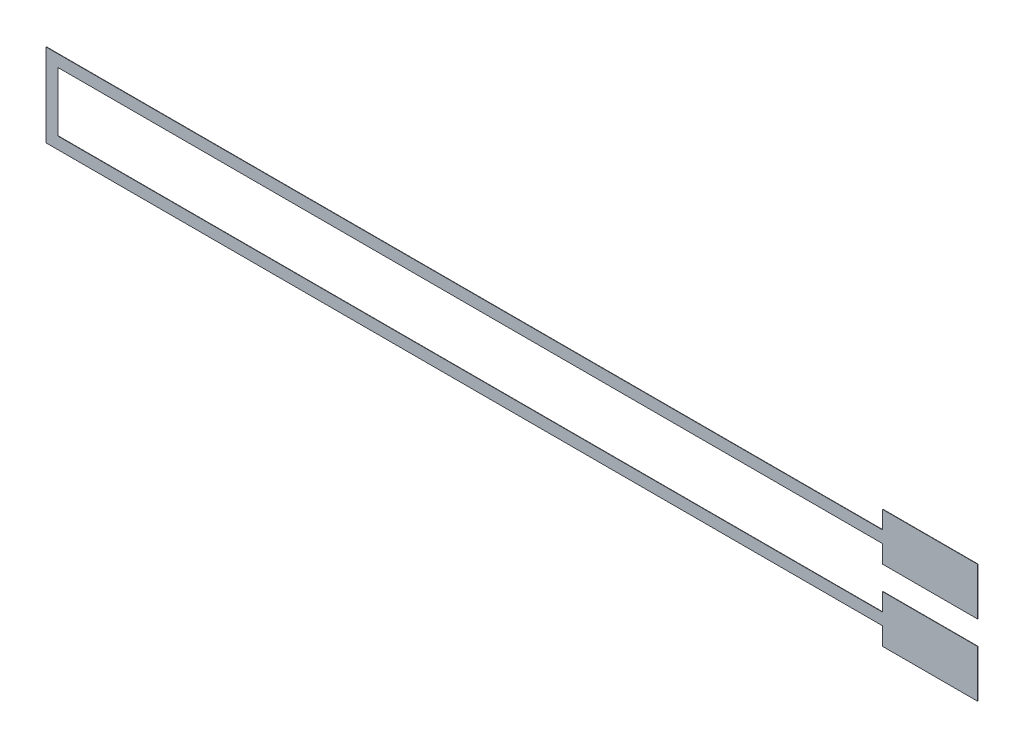
SolidWorks part; units mm, degrees
material "Pure Silver"
ref_plane "Front Plane" through (0, 0, 0) normal (0, 0, 1) x (1, 0, 0)
ref_plane "Top Plane" through (0, 0, 0) normal (0, 1, 0) x (1, 0, 0)
ref_plane "Right Plane" through (0, 0, 0) normal (1, 0, 0) x (0, 0, -1)
sketch "Sketch1" plane through (0, 0, 0) normal (0, 0, 1) x (1, 0, 0)
  line L0 (0, -1.5) -> (0, 1.5) construction
  line L2 (-2, 0.5) -> (2, 0.5)
  line L3 (-2, 0.5) -> (-2, 2.5)
  line L4 (-2, 2.5) -> (2, 2.5)
  line L5 (2, 0.5) -> (2, 2.5)
  line L6 (-2, 0.5) -> (2, 2.5) construction
  line L7 (-2, 2.5) -> (2, 0.5) construction
  line L8 (-2, -2.5) -> (2, -2.5)
  line L9 (-2, -2.5) -> (-2, -0.5)
  line L10 (-2, -0.5) -> (2, -0.5)
  line L11 (2, -2.5) -> (2, -0.5)
  line L12 (-2, -2.5) -> (2, -0.5) construction
  line L13 (-2, -0.5) -> (2, -2.5) construction
  point P4 (0, 0)
  dimension "D1" = 2
  dimension "D2" = 4
  dimension "D3" = 2
  dimension "D5" = 3
  dimension "D12" = 4
extrude "Boss-Extrude2" add sketch "Sketch1" along normal blind 0.015
sketch "Sketch4" plane through (0, 0, 0) normal (0, 0, 1) x (1, 0, 0)
  line L0 (-2, -1.5) -> (-2.75, -1.5) construction
  line L2 (-3, -1.75) -> (-3, -2) construction
  line L3 (-3, -2) -> (-4, -2) construction
  line L4 (-4, -2) -> (-4, -1) construction
  line L5 (-4, -1) -> (-5, -1) construction
  line L22 (-5, -1) -> (-5, -1.5) construction
  line L23 (-2, -0.5) -> (-2, -2.5) construction
  line L24 (-2, -0.5) -> (-2, -2.5)
  line L25 (-2, -1.2) -> (-2.75, -1.2)
  line L30 (-3.3, -1.75) -> (-3.3, -2)
  line L31 (-3.7, -2) -> (-3.7, -1)
  line L32 (-5.3, -1) -> (-5.3, -1.5)
  line L33 (-2, -1.8) -> (-2.7, -1.8)
  line L34 (-2.7, -1.8) -> (-2.7, -2)
  line L35 (-4.3, -2) -> (-4.3, -1)
  line L36 (-4.7, -1) -> (-4.7, -1.5)
  line L37 (-5.3, -1.5) -> (-4.7, -1.5)
  arc A0 (-2.75, -1.5) -> (-3, -1.75) centre (-2.75, -1.75) ccw construction
  arc A1 (-5, -1) -> (-4, -1) centre (-4.5, -1) cw construction
  arc A2 (-4, -2) -> (-3, -2) centre (-3.5, -2) ccw construction
  arc A15 (-2.75, -1.2) -> (-3.3, -1.75) centre (-2.75, -1.75) ccw
  arc A16 (-3.7, -2) -> (-3.3, -2) centre (-3.5, -2) ccw
  arc A17 (-5.3, -1) -> (-3.7, -1) centre (-4.5, -1) cw
  arc A18 (-2.7, -1.8) -> (-2.7, -1.8) centre (-2.7, -1.8) ccw
  arc A19 (-4.3, -2) -> (-2.7, -2) centre (-3.5, -2) ccw
  arc A20 (-4.7, -1) -> (-4.3, -1) centre (-4.5, -1) cw
  point P9 (-3, -1.5)
  dimension "D5" = 1
  dimension "D7" = 0.25
  dimension "D8" = 0.5
  dimension "D9" = 0.5
  dimension "D1" = 1
  dimension "D2" = 0.5
  dimension "D3" = 1
  dimension "D4" = 1
  dimension "D6" = 0.5
  dimension "D11" = 0.3
  dimension "D10" = 0.3
extrude "Boss-Extrude4" [suppressed] add sketch "Sketch4" along normal blind 0.015
sketch "Sketch7" plane through (0, 0, 0) normal (0, 0, 1) x (1, 0, 0)
  line L0 (-2, 1.5) -> (-2.75, 1.5) construction
  line L1 (-3, 1.75) -> (-3, 2) construction
  line L2 (-3, 2) -> (-4, 2) construction
  line L3 (-4, 2) -> (-4, 1) construction
  line L4 (-4, 1) -> (-5, 1) construction
  line L5 (-5, 1) -> (-5, 1.5) construction
  line L21 (-2, 1.8) -> (-2.7, 1.8)
  line L22 (-2.7, 1.8) -> (-2.7, 2)
  line L23 (-4.3, 2) -> (-4.3, 1)
  line L24 (-4.7, 1) -> (-4.7, 1.5)
  line L25 (-2, 1.2) -> (-2.75, 1.2)
  line L30 (-3.3, 1.75) -> (-3.3, 2)
  line L31 (-3.7, 2) -> (-3.7, 1)
  line L32 (-5.3, 1) -> (-5.3, 1.5)
  line L33 (-5.3, 1.5) -> (-4.7, 1.5)
  line L34 (-2, 2.5) -> (-2, 0.5) construction
  line L35 (-2, 2.5) -> (-2, 0.5)
  arc A0 (-5, 1) -> (-4, 1) centre (-4.5, 1) ccw construction
  arc A1 (-4, 2) -> (-3, 2) centre (-3.5, 2) cw construction
  arc A2 (-2.75, 1.5) -> (-3, 1.75) centre (-2.75, 1.75) cw construction
  arc A15 (-2.7, 1.8) -> (-2.7, 1.8) centre (-2.7, 1.8) cw
  arc A16 (-4.3, 2) -> (-2.7, 2) centre (-3.5, 2) cw
  arc A17 (-4.7, 1) -> (-4.3, 1) centre (-4.5, 1) ccw
  arc A18 (-2.75, 1.2) -> (-3.3, 1.75) centre (-2.75, 1.75) cw
  arc A19 (-3.7, 2) -> (-3.3, 2) centre (-3.5, 2) cw
  arc A20 (-5.3, 1) -> (-3.7, 1) centre (-4.5, 1) ccw
  point P13 (-3, 1.5)
  dimension "D5" = 1
  dimension "D7" = 0.5
  dimension "D8" = 0.5
  dimension "D3" = 1
  dimension "D9" = 0.25
  dimension "D1" = 1
  dimension "D2" = 0.5
  dimension "D4" = 1
  dimension "D6" = 0.5
  dimension "D11" = 0.3
  dimension "D10" = 0.3
extrude "Boss-Extrude9" [suppressed] add sketch "Sketch7" along normal blind 0.015
sketch "Sketch9" [suppressed] plane through (0, 0, 0) normal (0, 0, 1) x (1, 0, 0)
  line L2 (-5, -1.5) -> (-5, -2) construction
  line L3 (-5, -2) -> (-6, -2) construction
  line L4 (-6, -2) -> (-6, -1) construction
  line L5 (-6, -1) -> (-7, -1) construction
  line L6 (-7, -1) -> (-7, -1.5) construction
  line L7 (-5.3, -1.5) -> (-5.3, -2)
  line L8 (-5.7, -2) -> (-5.7, -1)
  line L9 (-7.3, -1) -> (-7.3, -1.5)
  line L10 (-4.7, -1.5) -> (-4.7, -2)
  line L11 (-6.3, -2) -> (-6.3, -1)
  line L12 (-6.7, -1) -> (-6.7, -1.5)
  line L13 (-7.3, -1.5) -> (-6.7, -1.5)
  line L14 (-5.3, -1.5) -> (-4.7, -1.5) construction
  line L15 (-5.3, -1.5) -> (-4.7, -1.5)
  arc A0 (-5, -2) -> (-6, -2) centre (-5.5, -2) cw construction
  arc A1 (-6, -1) -> (-7, -1) centre (-6.5, -1) ccw construction
  arc A2 (-5.3, -2) -> (-5.7, -2) centre (-5.5, -2) cw
  arc A3 (-5.7, -1) -> (-7.3, -1) centre (-6.5, -1) ccw
  arc A4 (-4.7, -2) -> (-6.3, -2) centre (-5.5, -2) cw
  arc A5 (-6.3, -1) -> (-6.7, -1) centre (-6.5, -1) ccw
  dimension "D6" = 0.5
  dimension "D7" = 0.5
  dimension "D1" = 0.5
  dimension "D2" = 1
  dimension "D3" = 1
  dimension "D4" = 1
  dimension "D5" = 0.5
  dimension "D8" = 0.3
  dimension "D9" = 0.3
extrude "Boss-Extrude10" [suppressed] add sketch "Sketch9" along normal up to surface (0.015 mm away) up to face at (0, -1.5, 0.015)
sketch "Sketch14" [suppressed] plane through (0, 0, 0.015) normal (0, 0, 1) x (1, 0, 0)
  line L1 (-5, 1.5) -> (-5, 2) construction
  line L2 (-5.3, 1.5) -> (-4.7, 1.5) construction
  line L3 (-5, 2) -> (-6, 2) construction
  line L4 (-6, 2) -> (-6, 1) construction
  line L5 (-6, 1) -> (-7, 1) construction
  line L6 (-7, 1) -> (-7, 1.5) construction
  line L7 (-4.7, 1.5) -> (-4.7, 2)
  line L8 (-6.3, 2) -> (-6.3, 1)
  line L9 (-6.7, 1) -> (-6.7, 1.5)
  line L10 (-5.3, 1.5) -> (-5.3, 2)
  line L11 (-5.7, 2) -> (-5.7, 1)
  line L12 (-7.3, 1) -> (-7.3, 1.5)
  line L13 (-7.3, 1.5) -> (-6.7, 1.5)
  arc A0 (-6, 2) -> (-5, 2) centre (-5.5, 2) cw construction
  arc A1 (-7, 1) -> (-6, 1) centre (-6.5, 1) ccw construction
  arc A2 (-6.3, 2) -> (-4.7, 2) centre (-5.5, 2) cw
  arc A3 (-6.7, 1) -> (-6.3, 1) centre (-6.5, 1) ccw
  arc A4 (-5.7, 2) -> (-5.3, 2) centre (-5.5, 2) cw
  arc A5 (-7.3, 1) -> (-5.7, 1) centre (-6.5, 1) ccw
  dimension "D6" = 0.5
  dimension "D7" = 0.5
  dimension "D1" = 0.5
  dimension "D2" = 1
  dimension "D3" = 1
  dimension "D4" = 1
  dimension "D5" = 0.5
  dimension "D8" = 0.3
  dimension "D9" = 0.3
extrude "Boss-Extrude16" [suppressed] add sketch "Sketch14" against normal up to surface (0.015 mm away) up to face at (0, 1.5, 0)
fillet "Fillet1" [suppressed] radius 0.25
fillet "Fillet2" [suppressed] radius 0.25
pattern_linear "LPattern3" [suppressed] count 16 spacing 2 of bodies 125 162
sketch "Sketch15" [suppressed] plane through (0, 0, 0.015) normal (0, 0, 1) x (1, 0, 0)
  line L0 (-36.3, 1) -> (-35.7, 1)
  line L1 (-35.7, -1) -> (-36.3, -1)
  line L2 (-36.3, -1) -> (-36.4846, -1)
  line L3 (-36.4846, -1) -> (-36.4846, -1.8714)
  line L4 (-36.4846, -1.8714) -> (-37.7365, -1.8714)
  line L5 (-37.7365, -1.8714) -> (-37.7365, 1.7158)
  line L6 (-37.7365, 1.7158) -> (-36.5999, 1.7158)
  line L7 (-36.5999, 1.7158) -> (-36.5999, 1)
  line L8 (-36.5999, 1) -> (-36.3, 1)
  line L9 (-35.7, -1) -> (-35.7, 1)
  arc A0 (-37.3, 1) -> (-35.7, 1) centre (-36.5, 1) ccw construction
  arc A1 (-35.7, -1) -> (-37.3, -1) centre (-36.5, -1) ccw construction
  arc A2 (-37.3, 1) -> (-35.7, 1) centre (-36.5, 1) ccw
  arc A3 (-35.7, -1) -> (-37.3, -1) centre (-36.5, -1) ccw
  arc A4 (-36.7, 1) -> (-36.3, 1) centre (-36.5, 1) ccw construction
  arc A5 (-36.3, -1) -> (-36.7, -1) centre (-36.5, -1) ccw construction
  arc A6 (-36.7, 1) -> (-36.3, 1) centre (-36.5, 1) ccw
  arc A7 (-36.3, -1) -> (-36.7, -1) centre (-36.5, -1) ccw
extrude "Cut-Extrude1" [suppressed] cut sketch "Sketch15" against normal through all contours L1 L9 L0 L8 L7 L6 L5 L4 L3 L2
sketch "Sketch16" [suppressed] plane through (0, 0, 0.015) normal (0, 0, 1) x (1, 0, 0)
  line L0 (-36.3, 1) -> (-35.7, 1) construction
  line L1 (-35.7, -1) -> (-36.3, -1) construction
  line L2 (-36.3, 1) -> (-35.7, 1)
  line L3 (-35.7, -1) -> (-36.3, -1)
  line L4 (-35.7, -1) -> (-35.7, 1)
  line L5 (-36.3, 1) -> (-36.3, -1)
extrude "Boss-Extrude17" [suppressed] add sketch "Sketch16" against normal up to surface (0.015 mm away) up to face at (0, 1.5, 0)
sketch "Sketch17" plane through (0, 0, 0) normal (0, 0, 1) x (1, 0, 0)
  line L0 (2, -2.5) -> (2, -0.5) construction
  line L1 (2, -0.5) -> (-2, -0.5) construction
  line L2 (-2, -0.5) -> (-2, -2.5) construction
  line L3 (-2, -2.5) -> (2, -2.5) construction
  line L4 (2, 0.5) -> (2, 2.5) construction
  line L5 (2, 2.5) -> (-2, 2.5) construction
  line L6 (-2, 2.5) -> (-2, 0.5) construction
  line L7 (-2, 0.5) -> (2, 0.5) construction
  line L8 (2, -2.5) -> (2, -0.5)
  line L9 (2, -0.5) -> (-2, -0.5)
  line L10 (-2, -0.5) -> (-2, -2.5)
  line L11 (-2, -2.5) -> (2, -2.5)
  line L12 (2, 0.5) -> (2, 2.5)
  line L13 (2, 2.5) -> (-2, 2.5)
  line L14 (-2, 2.5) -> (-2, 0.5)
  line L15 (-2, 0.5) -> (2, 0.5)
  line L16 (-2, 1.5) -> (-37, 1.5) construction
  line L17 (-2, -1.5) -> (-37, -1.5) construction
  line L18 (-37, -1.5) -> (-37, 1.5) construction
  line L19 (-2, 1.75) -> (-37.25, 1.75)
  line L20 (-37.25, -1.75) -> (-37.25, 1.75)
  line L21 (-2, -1.75) -> (-37.25, -1.75)
  line L22 (-2, 1.25) -> (-36.75, 1.25)
  line L23 (-36.75, -1.25) -> (-36.75, 1.25)
  line L24 (-2, -1.25) -> (-36.75, -1.25)
  dimension "D1" = 35
  dimension "D2" = 0.25
  dimension "D3" = 0.25
extrude "Boss-Extrude18" add sketch "Sketch17" along normal up to surface (0.015 mm away) contours L10 L24 L23 L22 L14 L19 L20 L21 region at (-19.625, -1.3958, 0) up to face at (0, -1.5, 0.015)
sketch "Sketch18" [suppressed] plane through (0, 0, 0) normal (0, 0, 1) x (1, 0, 0)
  line L0 (-2, 1.5) -> (-3, 1.5) construction
  line L1 (-3, 1.5) -> (-3, 1) construction
  line L2 (-3, 1) -> (-3, 0.5) construction
  line L3 (-3, 0.5) -> (-4, 0.5) construction
  line L4 (2, 0.5) -> (2, 2.5)
  line L5 (2, 2.5) -> (-2, 2.5)
  line L6 (-2, 2.5) -> (-2, 0.5)
  line L7 (-2, 0.5) -> (2, 0.5)
  line L8 (2, 0.5) -> (2, 2.5)
  line L9 (2, 2.5) -> (-2, 2.5)
  line L10 (-2, 2.5) -> (-2, 0.5)
  line L11 (-2, 0.5) -> (2, 0.5)
  line L12 (-4, 0.5) -> (-4, 2.5) construction
  line L13 (-4, 2.5) -> (-5, 2.5) construction
  line L14 (-5, 2.5) -> (-5, 1.5) construction
  line L15 (-2, 1.75) -> (-3.25, 1.75)
  line L16 (-3.25, 1.75) -> (-3.25, 1)
  line L17 (-3.25, 1) -> (-3.25, 0.75)
  line L18 (-3.25, 0.75) -> (-3.75, 0.75)
  line L19 (-3.75, 0.75) -> (-3.75, 2.75)
  line L20 (-3.75, 2.75) -> (-5.25, 2.75)
  line L21 (-5.25, 2.75) -> (-5.25, 1.5)
  line L22 (-2, 1.25) -> (-2.75, 1.25)
  line L23 (-2.75, 1.25) -> (-2.75, 1)
  line L24 (-2.75, 1) -> (-2.75, 0.25)
  line L25 (-2.75, 0.25) -> (-4.25, 0.25)
  line L26 (-4.25, 0.25) -> (-4.25, 2.25)
  line L27 (-4.25, 2.25) -> (-4.75, 2.25)
  line L28 (-4.75, 2.25) -> (-4.75, 1.5)
  line L29 (-5.25, 1.5) -> (-4.75, 1.5)
  dimension "D2" = 1
  dimension "D3" = 0.5
  dimension "D4" = 0.5
  dimension "D5" = 1
  dimension "D6" = 2
  dimension "D7" = 1
  dimension "D8" = 1
  dimension "D9" = 0.25
  dimension "D1" = 0
  dimension "D10" = 0.25
extrude "Boss-Extrude19" [suppressed] add sketch "Sketch18" along normal up to surface (0.015 mm away) contours L21 L29 L28 L27 L26 L25 L24 L23 L22 L10 L15 L16 L17 L18 L19 L20 up to face at (-9.75, 0, 0.015)
sketch "Sketch19" [suppressed] plane through (0, 0, 0.015) normal (0, 0, 1) x (1, 0, 0)
  line L0 (-2, -1.5) -> (-3, -1.5) construction
  line L1 (-3, -1.5) -> (-3, -0.5) construction
  line L2 (-3, -0.5) -> (-4, -0.5) construction
  line L3 (-4, -0.5) -> (-4, -2.5) construction
  line L4 (2, -2.5) -> (2, -0.5)
  line L5 (2, -0.5) -> (-2, -0.5)
  line L6 (-2, -0.5) -> (-2, -2.5)
  line L7 (-2, -2.5) -> (2, -2.5)
  line L8 (2, -2.5) -> (2, -0.5)
  line L9 (2, -0.5) -> (-2, -0.5)
  line L10 (-2, -0.5) -> (-2, -2.5)
  line L11 (-2, -2.5) -> (2, -2.5)
  line L12 (-4, -2.5) -> (-5, -2.5) construction
  line L13 (-5, -2.5) -> (-5, -1.5) construction
  line L14 (-2, -1.25) -> (-2.75, -1.25)
  line L15 (-2.75, -1.25) -> (-2.75, -0.25)
  line L16 (-2.75, -0.25) -> (-4.25, -0.25)
  line L17 (-4.25, -0.25) -> (-4.25, -2.25)
  line L18 (-4.25, -2.25) -> (-4.75, -2.25)
  line L19 (-4.75, -2.25) -> (-4.75, -1.5)
  line L20 (-2, -1.75) -> (-3.25, -1.75)
  line L21 (-3.25, -1.75) -> (-3.25, -0.75)
  line L22 (-3.25, -0.75) -> (-3.75, -0.75)
  line L23 (-3.75, -0.75) -> (-3.75, -2.75)
  line L24 (-3.75, -2.75) -> (-5.25, -2.75)
  line L25 (-5.25, -2.75) -> (-5.25, -1.5)
  line L26 (-5.25, -1.5) -> (-4.75, -1.5)
  dimension "D2" = 1
  dimension "D3" = 1
  dimension "D4" = 1
  dimension "D5" = 2
  dimension "D6" = 1
  dimension "D7" = 1
  dimension "D1" = 0
  dimension "D8" = 0.25
  dimension "D9" = 0.25
extrude "Boss-Extrude22" [suppressed] add sketch "Sketch19" against normal up to surface (0.015 mm away) contours L26 L25 L24 L23 L22 L21 L20 L10 L14 L15 L16 L17 L18 L19 up to face at (-9.75, 0, 0)
sketch "Sketch20" [suppressed] plane through (0, 0, 0.015) normal (0, 0, 1) x (1, 0, 0)
  line L0 (-5, 1.5) -> (-5, 0.5) construction
  line L1 (-5, 0.5) -> (-6, 0.5) construction
  line L2 (-6, 0.5) -> (-6, 2.5) construction
  line L3 (-6, 2.5) -> (-7, 2.5) construction
  line L4 (-7, 2.5) -> (-7, 1.5) construction
  line L5 (-5.25, 1.5) -> (-5.25, 0.75)
  line L6 (-5.25, 0.75) -> (-5.75, 0.75)
  line L7 (-5.75, 0.75) -> (-5.75, 2.75)
  line L8 (-5.75, 2.75) -> (-7.25, 2.75)
  line L9 (-7.25, 2.75) -> (-7.25, 1.5)
  line L10 (-4.75, 1.5) -> (-4.75, 0.25)
  line L11 (-4.75, 0.25) -> (-6.25, 0.25)
  line L12 (-6.25, 0.25) -> (-6.25, 2.25)
  line L13 (-6.25, 2.25) -> (-6.75, 2.25)
  line L14 (-6.75, 2.25) -> (-6.75, 1.5)
  line L15 (-7.25, 1.5) -> (-6.75, 1.5)
  line L18 (2, 0.5) -> (2, 2.5)
  line L19 (2, 2.5) -> (-2, 2.5)
  line L20 (-2, 2.5) -> (-2, 1.75)
  line L21 (-2, 1.75) -> (-3.25, 1.75)
  line L22 (-3.25, 1.75) -> (-3.25, 0.75)
  line L23 (-3.25, 0.75) -> (-3.75, 0.75)
  line L24 (-3.75, 0.75) -> (-3.75, 2.75)
  line L25 (-3.75, 2.75) -> (-5.25, 2.75)
  line L26 (-5.25, 2.75) -> (-5.25, 1.5)
  line L27 (-5.25, 1.5) -> (-4.75, 1.5)
  line L28 (-4.75, 1.5) -> (-4.75, 2.25)
  line L29 (-4.75, 2.25) -> (-4.25, 2.25)
  line L30 (-4.25, 2.25) -> (-4.25, 0.25)
  line L31 (-4.25, 0.25) -> (-2.75, 0.25)
  line L32 (-2.75, 0.25) -> (-2.75, 1.25)
  line L33 (-2.75, 1.25) -> (-2, 1.25)
  line L34 (-2, 1.25) -> (-2, 0.5)
  line L35 (-2, 0.5) -> (2, 0.5)
  line L36 (2, 0.5) -> (2, 2.5)
  line L37 (2, 2.5) -> (-2, 2.5)
  line L38 (-2, 2.5) -> (-2, 1.75)
  line L39 (-2, 1.75) -> (-3.25, 1.75)
  line L40 (-3.25, 1.75) -> (-3.25, 0.75)
  line L41 (-3.25, 0.75) -> (-3.75, 0.75)
  line L42 (-3.75, 0.75) -> (-3.75, 2.75)
  line L43 (-3.75, 2.75) -> (-5.25, 2.75)
  line L44 (-5.25, 2.75) -> (-5.25, 1.5)
  line L45 (-5.25, 1.5) -> (-4.75, 1.5)
  line L46 (-4.75, 1.5) -> (-4.75, 2.25)
  line L47 (-4.75, 2.25) -> (-4.25, 2.25)
  line L48 (-4.25, 2.25) -> (-4.25, 0.25)
  line L49 (-4.25, 0.25) -> (-2.75, 0.25)
  line L50 (-2.75, 0.25) -> (-2.75, 1.25)
  line L51 (-2.75, 1.25) -> (-2, 1.25)
  line L52 (-2, 1.25) -> (-2, 0.5)
  line L53 (-2, 0.5) -> (2, 0.5)
  line M28 (-5.25, 1.5) -> (-4.75, 1.5)
  dimension "D2" = 1
  dimension "D3" = 1
  dimension "D4" = 2
  dimension "D5" = 1
  dimension "D6" = 1
  dimension "D7" = 0.25
  dimension "D1" = 0
  dimension "D8" = 0.25
extrude "Boss-Extrude23" [suppressed] add sketch "Sketch20" against normal up to surface (0.015 mm away) contours L9 L15 L14 L13 L12 L11 L10 L5 L6 L7 L8 M28 up to face at (-9.75, 0, 0)
sketch "Sketch21" [suppressed] plane through (0, 0, 0.015) normal (0, 0, 1) x (1, 0, 0)
  line L0 (-5, -1.5) -> (-5, -0.5) construction
  line L1 (-5, -0.5) -> (-6, -0.5) construction
  line L2 (-6, -0.5) -> (-6, -2.5) construction
  line L3 (-6, -2.5) -> (-7, -2.5) construction
  line L4 (-7, -2.5) -> (-7, -1.5) construction
  line L5 (-4.75, -1.5) -> (-4.75, -0.25)
  line L6 (-4.75, -0.25) -> (-6.25, -0.25)
  line L7 (-6.25, -0.25) -> (-6.25, -2.25)
  line L8 (-6.25, -2.25) -> (-6.75, -2.25)
  line L9 (-6.75, -2.25) -> (-6.75, -1.5)
  line L10 (-5.25, -1.5) -> (-5.25, -0.75)
  line L11 (-5.25, -0.75) -> (-5.75, -0.75)
  line L12 (-5.75, -0.75) -> (-5.75, -2.75)
  line L13 (-5.75, -2.75) -> (-7.25, -2.75)
  line L14 (-7.25, -2.75) -> (-7.25, -1.5)
  line L15 (-7.25, -1.5) -> (-6.75, -1.5)
  line L18 (2, -2.5) -> (2, -0.5)
  line L19 (2, -0.5) -> (-2, -0.5)
  line L20 (-2, -0.5) -> (-2, -1.25)
  line L21 (-2, -1.25) -> (-2.75, -1.25)
  line L22 (-2.75, -1.25) -> (-2.75, -0.25)
  line L23 (-2.75, -0.25) -> (-4.25, -0.25)
  line L24 (-4.25, -0.25) -> (-4.25, -2.25)
  line L25 (-4.25, -2.25) -> (-4.75, -2.25)
  line L26 (-4.75, -2.25) -> (-4.75, -1.5)
  line L27 (-4.75, -1.5) -> (-5.25, -1.5)
  line L28 (-5.25, -1.5) -> (-5.25, -2.75)
  line L29 (-5.25, -2.75) -> (-3.75, -2.75)
  line L30 (-3.75, -2.75) -> (-3.75, -0.75)
  line L31 (-3.75, -0.75) -> (-3.25, -0.75)
  line L32 (-3.25, -0.75) -> (-3.25, -1.75)
  line L33 (-3.25, -1.75) -> (-2, -1.75)
  line L34 (-2, -1.75) -> (-2, -2.5)
  line L35 (-2, -2.5) -> (2, -2.5)
  line L36 (2, -2.5) -> (2, -0.5)
  line L37 (2, -0.5) -> (-2, -0.5)
  line L38 (-2, -0.5) -> (-2, -1.25)
  line L39 (-2, -1.25) -> (-2.75, -1.25)
  line L40 (-2.75, -1.25) -> (-2.75, -0.25)
  line L41 (-2.75, -0.25) -> (-4.25, -0.25)
  line L42 (-4.25, -0.25) -> (-4.25, -2.25)
  line L43 (-4.25, -2.25) -> (-4.75, -2.25)
  line L44 (-4.75, -2.25) -> (-4.75, -1.5)
  line L45 (-4.75, -1.5) -> (-5.25, -1.5)
  line L46 (-5.25, -1.5) -> (-5.25, -2.75)
  line L47 (-5.25, -2.75) -> (-3.75, -2.75)
  line L48 (-3.75, -2.75) -> (-3.75, -0.75)
  line L49 (-3.75, -0.75) -> (-3.25, -0.75)
  line L50 (-3.25, -0.75) -> (-3.25, -1.75)
  line L51 (-3.25, -1.75) -> (-2, -1.75)
  line L52 (-2, -1.75) -> (-2, -2.5)
  line L53 (-2, -2.5) -> (2, -2.5)
  line M29 (-4.75, -1.5) -> (-5.25, -1.5)
  dimension "D2" = 1
  dimension "D3" = 1
  dimension "D4" = 2
  dimension "D5" = 1
  dimension "D6" = 1
  dimension "D7" = 0.25
  dimension "D1" = 0
  dimension "D8" = 0.25
extrude "Boss-Extrude24" [suppressed] add sketch "Sketch21" against normal up to surface (0.015 mm away) contours L15 L14 L13 L12 L11 L10 L5 L6 L7 L8 L9 M29 up to face at (-9.75, 0, 0)
pattern_linear "LPattern4" [suppressed] count 13 spacing 2 of bodies 190 191
sketch "Sketch22" [suppressed] plane through (0, 0, 0.015) normal (0, 0, 1) x (1, 0, 0)
  line L0 (-31.25, -1.5) -> (-30.75, -1.5) construction
  line L1 (-31.25, -1.5) -> (-30.75, -1.5)
  line L2 (-31.25, 1.5) -> (-30.75, 1.5) construction
  line L3 (-31.25, 1.5) -> (-30.75, 1.5)
  line L4 (-31.25, 1.5) -> (-31.25, -1.5)
  line L5 (-30.75, 1.5) -> (-30.75, -1.5)
extrude "Boss-Extrude25" [suppressed] add sketch "Sketch22" against normal up to surface (0.015 mm away) up to face at (-9.75, 0, 0)
sketch "Sketch23" [suppressed] plane through (0, 0, 0.015) normal (0, 0, 1) x (1, 0, 0)
  line L0 (-36.3, 0) -> (2, 0)
  line L1 (-36.3, 2) -> (-36.3, -2) construction
  line L2 (2, 1.5) -> (2, 0)
  line L3 (2, 0.75) -> (2, 2.25) construction
  line L5 (-39.65, -7.5) -> (5.35, -7.5)
  line L6 (-39.65, -7.5) -> (-39.65, 7.5)
  line L7 (-39.65, 7.5) -> (5.35, 7.5)
  line L8 (5.35, -7.5) -> (5.35, 7.5)
  line L9 (-39.65, -7.5) -> (5.35, 7.5) construction
  line L10 (-39.65, 7.5) -> (5.35, -7.5) construction
  point P1 (-17.15, 0)
  point P9 (-17.15, 0)
  dimension "D1" = 15
  dimension "D2" = 45
extrude "Boss-Extrude26" [suppressed] add sketch "Sketch23" along normal blind 2
sketch "Sketch24" [suppressed] plane through (0, 0, 0) normal (0, 0, -1) x (-1, 0, 0)
  line L148 (35.7, 2) -> (35.7, -2)
  line L149 (35.3, -2) -> (35.3, -1)
  line L150 (33.7, -1) -> (33.7, -2)
  line L151 (33.3, -2) -> (33.3, -1)
  line L152 (31.7, -1) -> (31.7, -2)
  line L153 (31.3, -2) -> (31.3, -1)
  line L154 (29.7, -1) -> (29.7, -2)
  line L155 (29.3, -2) -> (29.3, -1)
  line L156 (27.7, -1) -> (27.7, -2)
  line L157 (27.3, -2) -> (27.3, -1)
  line L158 (25.7, -1) -> (25.7, -2)
  line L159 (25.3, -2) -> (25.3, -1)
  line L160 (23.7, -1) -> (23.7, -2)
  line L161 (23.3, -2) -> (23.3, -1)
  line L162 (21.7, -1) -> (21.7, -2)
  line L163 (21.3, -2) -> (21.3, -1)
  line L164 (19.7, -1) -> (19.7, -2)
  line L165 (19.3, -2) -> (19.3, -1)
  line L166 (17.7, -1) -> (17.7, -2)
  line L167 (17.3, -2) -> (17.3, -1)
  line L168 (15.7, -1) -> (15.7, -2)
  line L169 (15.3, -2) -> (15.3, -1)
  line L170 (13.7, -1) -> (13.7, -2)
  line L171 (13.3, -2) -> (13.3, -1)
  line L172 (11.7, -1) -> (11.7, -2)
  line L173 (11.3, -2) -> (11.3, -1)
  line L174 (9.7, -1) -> (9.7, -2)
  line L175 (9.3, -2) -> (9.3, -1)
  line L176 (7.7, -1) -> (7.7, -2)
  line L177 (7.3, -2) -> (7.3, -1)
  line L178 (5.7, -1) -> (5.7, -2)
  line L179 (5.3, -2) -> (5.3, -1)
  line L180 (3.7, -1) -> (3.7, -2)
  line L181 (3.3, -2) -> (3.3, -1.75)
  line L182 (2.75, -1.2) -> (2.25, -1.2)
  line L183 (2, -0.95) -> (2, -0.75)
  line L184 (1.75, -0.5) -> (-1.75, -0.5)
  line L185 (-2, -0.75) -> (-2, -2.25)
  line L186 (-1.75, -2.5) -> (1.75, -2.5)
  line L187 (2, -2.25) -> (2, -2.05)
  line L188 (2.25, -1.8) -> (2.7, -1.8)
  line L189 (2.7, -1.8) -> (2.7, -2)
  line L190 (4.3, -2) -> (4.3, -1)
  line L191 (4.7, -1) -> (4.7, -2)
  line L192 (6.3, -2) -> (6.3, -1)
  line L193 (6.7, -1) -> (6.7, -2)
  line L194 (8.3, -2) -> (8.3, -1)
  line L195 (8.7, -1) -> (8.7, -2)
  line L196 (10.3, -2) -> (10.3, -1)
  line L197 (10.7, -1) -> (10.7, -2)
  line L198 (12.3, -2) -> (12.3, -1)
  line L199 (12.7, -1) -> (12.7, -2)
  line L200 (14.3, -2) -> (14.3, -1)
  line L201 (14.7, -1) -> (14.7, -2)
  line L202 (16.3, -2) -> (16.3, -1)
  line L203 (16.7, -1) -> (16.7, -2)
  line L204 (18.3, -2) -> (18.3, -1)
  line L205 (18.7, -1) -> (18.7, -2)
  line L206 (20.3, -2) -> (20.3, -1)
  line L207 (20.7, -1) -> (20.7, -2)
  line L208 (22.3, -2) -> (22.3, -1)
  line L209 (22.7, -1) -> (22.7, -2)
  line L210 (24.3, -2) -> (24.3, -1)
  line L211 (24.7, -1) -> (24.7, -2)
  line L212 (26.3, -2) -> (26.3, -1)
  line L213 (26.7, -1) -> (26.7, -2)
  line L214 (28.3, -2) -> (28.3, -1)
  line L215 (28.7, -1) -> (28.7, -2)
  line L216 (30.3, -2) -> (30.3, -1)
  line L217 (30.7, -1) -> (30.7, -2)
  line L218 (32.3, -2) -> (32.3, -1)
  line L219 (32.7, -1) -> (32.7, -2)
  line L220 (34.3, -2) -> (34.3, -1)
  line L221 (34.7, -1) -> (34.7, -2)
  line L222 (36.3, -2) -> (36.3, 2)
  line L223 (34.7, 2) -> (34.7, 1)
  line L224 (34.3, 1) -> (34.3, 2)
  line L225 (32.7, 2) -> (32.7, 1)
  line L226 (32.3, 1) -> (32.3, 2)
  line L227 (30.7, 2) -> (30.7, 1)
  line L228 (30.3, 1) -> (30.3, 2)
  line L229 (28.7, 2) -> (28.7, 1)
  line L230 (28.3, 1) -> (28.3, 2)
  line L231 (26.7, 2) -> (26.7, 1)
  line L232 (26.3, 1) -> (26.3, 2)
  line L233 (24.7, 2) -> (24.7, 1)
  line L234 (24.3, 1) -> (24.3, 2)
  line L235 (22.7, 2) -> (22.7, 1)
  line L236 (22.3, 1) -> (22.3, 2)
  line L237 (20.7, 2) -> (20.7, 1)
  line L238 (20.3, 1) -> (20.3, 2)
  line L239 (18.7, 2) -> (18.7, 1)
  line L240 (18.3, 1) -> (18.3, 2)
  line L241 (16.7, 2) -> (16.7, 1)
  line L242 (16.3, 1) -> (16.3, 2)
  line L243 (14.7, 2) -> (14.7, 1)
  line L244 (14.3, 1) -> (14.3, 2)
  line L245 (12.7, 2) -> (12.7, 1)
  line L246 (12.3, 1) -> (12.3, 2)
  line L247 (10.7, 2) -> (10.7, 1)
  line L248 (10.3, 1) -> (10.3, 2)
  line L249 (8.7, 2) -> (8.7, 1)
  line L250 (8.3, 1) -> (8.3, 2)
  line L251 (6.7, 2) -> (6.7, 1)
  line L252 (6.3, 1) -> (6.3, 2)
  line L253 (4.7, 2) -> (4.7, 1)
  line L254 (4.3, 1) -> (4.3, 2)
  line L255 (2.7, 2) -> (2.7, 1.8)
  line L256 (2.7, 1.8) -> (2.25, 1.8)
  line L257 (2, 2.05) -> (2, 2.25)
  line L258 (1.75, 2.5) -> (-1.75, 2.5)
  line L259 (-2, 2.25) -> (-2, 0.75)
  line L260 (-1.75, 0.5) -> (1.75, 0.5)
  line L261 (2, 0.75) -> (2, 0.95)
  line L262 (2.25, 1.2) -> (2.75, 1.2)
  line L263 (3.3, 1.75) -> (3.3, 2)
  line L264 (3.7, 2) -> (3.7, 1)
  line L265 (5.3, 1) -> (5.3, 2)
  line L266 (5.7, 2) -> (5.7, 1)
  line L267 (7.3, 1) -> (7.3, 2)
  line L268 (7.7, 2) -> (7.7, 1)
  line L269 (9.3, 1) -> (9.3, 2)
  line L270 (9.7, 2) -> (9.7, 1)
  line L271 (11.3, 1) -> (11.3, 2)
  line L272 (11.7, 2) -> (11.7, 1)
  line L273 (13.3, 1) -> (13.3, 2)
  line L274 (13.7, 2) -> (13.7, 1)
  line L275 (15.3, 1) -> (15.3, 2)
  line L276 (15.7, 2) -> (15.7, 1)
  line L277 (17.3, 1) -> (17.3, 2)
  line L278 (17.7, 2) -> (17.7, 1)
  line L279 (19.3, 1) -> (19.3, 2)
  line L280 (19.7, 2) -> (19.7, 1)
  line L281 (21.3, 1) -> (21.3, 2)
  line L282 (21.7, 2) -> (21.7, 1)
  line L283 (23.3, 1) -> (23.3, 2)
  line L284 (23.7, 2) -> (23.7, 1)
  line L285 (25.3, 1) -> (25.3, 2)
  line L286 (25.7, 2) -> (25.7, 1)
  line L287 (27.3, 1) -> (27.3, 2)
  line L288 (27.7, 2) -> (27.7, 1)
  line L289 (29.3, 1) -> (29.3, 2)
  line L290 (29.7, 2) -> (29.7, 1)
  line L291 (31.3, 1) -> (31.3, 2)
  line L292 (31.7, 2) -> (31.7, 1)
  line L293 (33.3, 1) -> (33.3, 2)
  line L294 (33.7, 2) -> (33.7, 1)
  line L295 (35.3, 1) -> (35.3, 2)
  line L296 (35.7, 2) -> (35.7, -2)
  line L297 (35.3, -2) -> (35.3, -1)
  line L298 (33.7, -1) -> (33.7, -2)
  line L299 (33.3, -2) -> (33.3, -1)
  line L300 (31.7, -1) -> (31.7, -2)
  line L301 (31.3, -2) -> (31.3, -1)
  line L302 (29.7, -1) -> (29.7, -2)
  line L303 (29.3, -2) -> (29.3, -1)
  line L304 (27.7, -1) -> (27.7, -2)
  line L305 (27.3, -2) -> (27.3, -1)
  line L306 (25.7, -1) -> (25.7, -2)
  line L307 (25.3, -2) -> (25.3, -1)
  line L308 (23.7, -1) -> (23.7, -2)
  line L309 (23.3, -2) -> (23.3, -1)
  line L310 (21.7, -1) -> (21.7, -2)
  line L311 (21.3, -2) -> (21.3, -1)
  line L312 (19.7, -1) -> (19.7, -2)
  line L313 (19.3, -2) -> (19.3, -1)
  line L314 (17.7, -1) -> (17.7, -2)
  line L315 (17.3, -2) -> (17.3, -1)
  line L316 (15.7, -1) -> (15.7, -2)
  line L317 (15.3, -2) -> (15.3, -1)
  line L318 (13.7, -1) -> (13.7, -2)
  line L319 (13.3, -2) -> (13.3, -1)
  line L320 (11.7, -1) -> (11.7, -2)
  line L321 (11.3, -2) -> (11.3, -1)
  line L322 (9.7, -1) -> (9.7, -2)
  line L323 (9.3, -2) -> (9.3, -1)
  line L324 (7.7, -1) -> (7.7, -2)
  line L325 (7.3, -2) -> (7.3, -1)
  line L326 (5.7, -1) -> (5.7, -2)
  line L327 (5.3, -2) -> (5.3, -1)
  line L328 (3.7, -1) -> (3.7, -2)
  line L329 (3.3, -2) -> (3.3, -1.75)
  line L330 (2.75, -1.2) -> (2.25, -1.2)
  line L331 (2, -0.95) -> (2, -0.75)
  line L332 (1.75, -0.5) -> (-1.75, -0.5)
  line L333 (-2, -0.75) -> (-2, -2.25)
  line L334 (-1.75, -2.5) -> (1.75, -2.5)
  line L335 (2, -2.25) -> (2, -2.05)
  line L336 (2.25, -1.8) -> (2.7, -1.8)
  line L337 (2.7, -1.8) -> (2.7, -2)
  line L338 (4.3, -2) -> (4.3, -1)
  line L339 (4.7, -1) -> (4.7, -2)
  line L340 (6.3, -2) -> (6.3, -1)
  line L341 (6.7, -1) -> (6.7, -2)
  line L342 (8.3, -2) -> (8.3, -1)
  line L343 (8.7, -1) -> (8.7, -2)
  line L344 (10.3, -2) -> (10.3, -1)
  line L345 (10.7, -1) -> (10.7, -2)
  line L346 (12.3, -2) -> (12.3, -1)
  line L347 (12.7, -1) -> (12.7, -2)
  line L348 (14.3, -2) -> (14.3, -1)
  line L349 (14.7, -1) -> (14.7, -2)
  line L350 (16.3, -2) -> (16.3, -1)
  line L351 (16.7, -1) -> (16.7, -2)
  line L352 (18.3, -2) -> (18.3, -1)
  line L353 (18.7, -1) -> (18.7, -2)
  line L354 (20.3, -2) -> (20.3, -1)
  line L355 (20.7, -1) -> (20.7, -2)
  line L356 (22.3, -2) -> (22.3, -1)
  line L357 (22.7, -1) -> (22.7, -2)
  line L358 (24.3, -2) -> (24.3, -1)
  line L359 (24.7, -1) -> (24.7, -2)
  line L360 (26.3, -2) -> (26.3, -1)
  line L361 (26.7, -1) -> (26.7, -2)
  line L362 (28.3, -2) -> (28.3, -1)
  line L363 (28.7, -1) -> (28.7, -2)
  line L364 (30.3, -2) -> (30.3, -1)
  line L365 (30.7, -1) -> (30.7, -2)
  line L366 (32.3, -2) -> (32.3, -1)
  line L367 (32.7, -1) -> (32.7, -2)
  line L368 (34.3, -2) -> (34.3, -1)
  line L369 (34.7, -1) -> (34.7, -2)
  line L370 (36.3, -2) -> (36.3, 2)
  line L371 (34.7, 2) -> (34.7, 1)
  line L372 (34.3, 1) -> (34.3, 2)
  line L373 (32.7, 2) -> (32.7, 1)
  line L374 (32.3, 1) -> (32.3, 2)
  line L375 (30.7, 2) -> (30.7, 1)
  line L376 (30.3, 1) -> (30.3, 2)
  line L377 (28.7, 2) -> (28.7, 1)
  line L378 (28.3, 1) -> (28.3, 2)
  line L379 (26.7, 2) -> (26.7, 1)
  line L380 (26.3, 1) -> (26.3, 2)
  line L381 (24.7, 2) -> (24.7, 1)
  line L382 (24.3, 1) -> (24.3, 2)
  line L383 (22.7, 2) -> (22.7, 1)
  line L384 (22.3, 1) -> (22.3, 2)
  line L385 (20.7, 2) -> (20.7, 1)
  line L386 (20.3, 1) -> (20.3, 2)
  line L387 (18.7, 2) -> (18.7, 1)
  line L388 (18.3, 1) -> (18.3, 2)
  line L389 (16.7, 2) -> (16.7, 1)
  line L390 (16.3, 1) -> (16.3, 2)
  line L391 (14.7, 2) -> (14.7, 1)
  line L392 (14.3, 1) -> (14.3, 2)
  line L393 (12.7, 2) -> (12.7, 1)
  line L394 (12.3, 1) -> (12.3, 2)
  line L395 (10.7, 2) -> (10.7, 1)
  line L396 (10.3, 1) -> (10.3, 2)
  line L397 (8.7, 2) -> (8.7, 1)
  line L398 (8.3, 1) -> (8.3, 2)
  line L399 (6.7, 2) -> (6.7, 1)
  line L400 (6.3, 1) -> (6.3, 2)
  line L401 (4.7, 2) -> (4.7, 1)
  line L402 (4.3, 1) -> (4.3, 2)
  line L403 (2.7, 2) -> (2.7, 1.8)
  line L404 (2.7, 1.8) -> (2.25, 1.8)
  line L405 (2, 2.05) -> (2, 2.25)
  line L406 (1.75, 2.5) -> (-1.75, 2.5)
  line L407 (-2, 2.25) -> (-2, 0.75)
  line L408 (-1.75, 0.5) -> (1.75, 0.5)
  line L409 (2, 0.75) -> (2, 0.95)
  line L410 (2.25, 1.2) -> (2.75, 1.2)
  line L411 (3.3, 1.75) -> (3.3, 2)
  line L412 (3.7, 2) -> (3.7, 1)
  line L413 (5.3, 1) -> (5.3, 2)
  line L414 (5.7, 2) -> (5.7, 1)
  line L415 (7.3, 1) -> (7.3, 2)
  line L416 (7.7, 2) -> (7.7, 1)
  line L417 (9.3, 1) -> (9.3, 2)
  line L418 (9.7, 2) -> (9.7, 1)
  line L419 (11.3, 1) -> (11.3, 2)
  line L420 (11.7, 2) -> (11.7, 1)
  line L421 (13.3, 1) -> (13.3, 2)
  line L422 (13.7, 2) -> (13.7, 1)
  line L423 (15.3, 1) -> (15.3, 2)
  line L424 (15.7, 2) -> (15.7, 1)
  line L425 (17.3, 1) -> (17.3, 2)
  line L426 (17.7, 2) -> (17.7, 1)
  line L427 (19.3, 1) -> (19.3, 2)
  line L428 (19.7, 2) -> (19.7, 1)
  line L429 (21.3, 1) -> (21.3, 2)
  line L430 (21.7, 2) -> (21.7, 1)
  line L431 (23.3, 1) -> (23.3, 2)
  line L432 (23.7, 2) -> (23.7, 1)
  line L433 (25.3, 1) -> (25.3, 2)
  line L434 (25.7, 2) -> (25.7, 1)
  line L435 (27.3, 1) -> (27.3, 2)
  line L436 (27.7, 2) -> (27.7, 1)
  line L437 (29.3, 1) -> (29.3, 2)
  line L438 (29.7, 2) -> (29.7, 1)
  line L439 (31.3, 1) -> (31.3, 2)
  line L440 (31.7, 2) -> (31.7, 1)
  line L441 (33.3, 1) -> (33.3, 2)
  line L442 (33.7, 2) -> (33.7, 1)
  line L443 (35.3, 1) -> (35.3, 2)
  arc A146 (35.3, -2) -> (35.7, -2) centre (35.5, -2) ccw
  arc A147 (35.3, -1) -> (33.7, -1) centre (34.5, -1) ccw
  arc A148 (33.3, -2) -> (33.7, -2) centre (33.5, -2) ccw
  arc A149 (33.3, -1) -> (31.7, -1) centre (32.5, -1) ccw
  arc A150 (31.3, -2) -> (31.7, -2) centre (31.5, -2) ccw
  arc A151 (31.3, -1) -> (29.7, -1) centre (30.5, -1) ccw
  arc A152 (29.3, -2) -> (29.7, -2) centre (29.5, -2) ccw
  arc A153 (29.3, -1) -> (27.7, -1) centre (28.5, -1) ccw
  arc A154 (27.3, -2) -> (27.7, -2) centre (27.5, -2) ccw
  arc A155 (27.3, -1) -> (25.7, -1) centre (26.5, -1) ccw
  arc A156 (25.3, -2) -> (25.7, -2) centre (25.5, -2) ccw
  arc A157 (25.3, -1) -> (23.7, -1) centre (24.5, -1) ccw
  arc A158 (23.3, -2) -> (23.7, -2) centre (23.5, -2) ccw
  arc A159 (23.3, -1) -> (21.7, -1) centre (22.5, -1) ccw
  arc A160 (21.3, -2) -> (21.7, -2) centre (21.5, -2) ccw
  arc A161 (21.3, -1) -> (19.7, -1) centre (20.5, -1) ccw
  arc A162 (19.3, -2) -> (19.7, -2) centre (19.5, -2) ccw
  arc A163 (19.3, -1) -> (17.7, -1) centre (18.5, -1) ccw
  arc A164 (17.3, -2) -> (17.7, -2) centre (17.5, -2) ccw
  arc A165 (17.3, -1) -> (15.7, -1) centre (16.5, -1) ccw
  arc A166 (15.3, -2) -> (15.7, -2) centre (15.5, -2) ccw
  arc A167 (15.3, -1) -> (13.7, -1) centre (14.5, -1) ccw
  arc A168 (13.3, -2) -> (13.7, -2) centre (13.5, -2) ccw
  arc A169 (13.3, -1) -> (11.7, -1) centre (12.5, -1) ccw
  arc A170 (11.3, -2) -> (11.7, -2) centre (11.5, -2) ccw
  arc A171 (11.3, -1) -> (9.7, -1) centre (10.5, -1) ccw
  arc A172 (9.3, -2) -> (9.7, -2) centre (9.5, -2) ccw
  arc A173 (9.3, -1) -> (7.7, -1) centre (8.5, -1) ccw
  arc A174 (7.3, -2) -> (7.7, -2) centre (7.5, -2) ccw
  arc A175 (7.3, -1) -> (5.7, -1) centre (6.5, -1) ccw
  arc A176 (5.3, -2) -> (5.7, -2) centre (5.5, -2) ccw
  arc A177 (5.3, -1) -> (3.7, -1) centre (4.5, -1) ccw
  arc A178 (3.3, -2) -> (3.7, -2) centre (3.5, -2) ccw
  arc A179 (3.3, -1.75) -> (2.75, -1.2) centre (2.75, -1.75) ccw
  arc A180 (2, -0.95) -> (2.25, -1.2) centre (2.25, -0.95) ccw
  arc A181 (2, -0.75) -> (1.75, -0.5) centre (1.75, -0.75) ccw
  arc A182 (-1.75, -0.5) -> (-2, -0.75) centre (-1.75, -0.75) ccw
  arc A183 (-2, -2.25) -> (-1.75, -2.5) centre (-1.75, -2.25) ccw
  arc A184 (1.75, -2.5) -> (2, -2.25) centre (1.75, -2.25) ccw
  arc A185 (2.25, -1.8) -> (2, -2.05) centre (2.25, -2.05) ccw
  arc A186 (2.7, -2) -> (4.3, -2) centre (3.5, -2) ccw
  arc A187 (4.7, -1) -> (4.3, -1) centre (4.5, -1) ccw
  arc A188 (4.7, -2) -> (6.3, -2) centre (5.5, -2) ccw
  arc A189 (6.7, -1) -> (6.3, -1) centre (6.5, -1) ccw
  arc A190 (6.7, -2) -> (8.3, -2) centre (7.5, -2) ccw
  arc A191 (8.7, -1) -> (8.3, -1) centre (8.5, -1) ccw
  arc A192 (8.7, -2) -> (10.3, -2) centre (9.5, -2) ccw
  arc A193 (10.7, -1) -> (10.3, -1) centre (10.5, -1) ccw
  arc A194 (10.7, -2) -> (12.3, -2) centre (11.5, -2) ccw
  arc A195 (12.7, -1) -> (12.3, -1) centre (12.5, -1) ccw
  arc A196 (12.7, -2) -> (14.3, -2) centre (13.5, -2) ccw
  arc A197 (14.7, -1) -> (14.3, -1) centre (14.5, -1) ccw
  arc A198 (14.7, -2) -> (16.3, -2) centre (15.5, -2) ccw
  arc A199 (16.7, -1) -> (16.3, -1) centre (16.5, -1) ccw
  arc A200 (16.7, -2) -> (18.3, -2) centre (17.5, -2) ccw
  arc A201 (18.7, -1) -> (18.3, -1) centre (18.5, -1) ccw
  arc A202 (18.7, -2) -> (20.3, -2) centre (19.5, -2) ccw
  arc A203 (20.7, -1) -> (20.3, -1) centre (20.5, -1) ccw
  arc A204 (20.7, -2) -> (22.3, -2) centre (21.5, -2) ccw
  arc A205 (22.7, -1) -> (22.3, -1) centre (22.5, -1) ccw
  arc A206 (22.7, -2) -> (24.3, -2) centre (23.5, -2) ccw
  arc A207 (24.7, -1) -> (24.3, -1) centre (24.5, -1) ccw
  arc A208 (24.7, -2) -> (26.3, -2) centre (25.5, -2) ccw
  arc A209 (26.7, -1) -> (26.3, -1) centre (26.5, -1) ccw
  arc A210 (26.7, -2) -> (28.3, -2) centre (27.5, -2) ccw
  arc A211 (28.7, -1) -> (28.3, -1) centre (28.5, -1) ccw
  arc A212 (28.7, -2) -> (30.3, -2) centre (29.5, -2) ccw
  arc A213 (30.7, -1) -> (30.3, -1) centre (30.5, -1) ccw
  arc A214 (30.7, -2) -> (32.3, -2) centre (31.5, -2) ccw
  arc A215 (32.7, -1) -> (32.3, -1) centre (32.5, -1) ccw
  arc A216 (32.7, -2) -> (34.3, -2) centre (33.5, -2) ccw
  arc A217 (34.7, -1) -> (34.3, -1) centre (34.5, -1) ccw
  arc A218 (34.7, -2) -> (36.3, -2) centre (35.5, -2) ccw
  arc A219 (36.3, 2) -> (34.7, 2) centre (35.5, 2) ccw
  arc A220 (34.3, 1) -> (34.7, 1) centre (34.5, 1) ccw
  arc A221 (34.3, 2) -> (32.7, 2) centre (33.5, 2) ccw
  arc A222 (32.3, 1) -> (32.7, 1) centre (32.5, 1) ccw
  arc A223 (32.3, 2) -> (30.7, 2) centre (31.5, 2) ccw
  arc A224 (30.3, 1) -> (30.7, 1) centre (30.5, 1) ccw
  arc A225 (30.3, 2) -> (28.7, 2) centre (29.5, 2) ccw
  arc A226 (28.3, 1) -> (28.7, 1) centre (28.5, 1) ccw
  arc A227 (28.3, 2) -> (26.7, 2) centre (27.5, 2) ccw
  arc A228 (26.3, 1) -> (26.7, 1) centre (26.5, 1) ccw
  arc A229 (26.3, 2) -> (24.7, 2) centre (25.5, 2) ccw
  arc A230 (24.3, 1) -> (24.7, 1) centre (24.5, 1) ccw
  arc A231 (24.3, 2) -> (22.7, 2) centre (23.5, 2) ccw
  arc A232 (22.3, 1) -> (22.7, 1) centre (22.5, 1) ccw
  arc A233 (22.3, 2) -> (20.7, 2) centre (21.5, 2) ccw
  arc A234 (20.3, 1) -> (20.7, 1) centre (20.5, 1) ccw
  arc A235 (20.3, 2) -> (18.7, 2) centre (19.5, 2) ccw
  arc A236 (18.3, 1) -> (18.7, 1) centre (18.5, 1) ccw
  arc A237 (18.3, 2) -> (16.7, 2) centre (17.5, 2) ccw
  arc A238 (16.3, 1) -> (16.7, 1) centre (16.5, 1) ccw
  arc A239 (16.3, 2) -> (14.7, 2) centre (15.5, 2) ccw
  arc A240 (14.3, 1) -> (14.7, 1) centre (14.5, 1) ccw
  arc A241 (14.3, 2) -> (12.7, 2) centre (13.5, 2) ccw
  arc A242 (12.3, 1) -> (12.7, 1) centre (12.5, 1) ccw
  arc A243 (12.3, 2) -> (10.7, 2) centre (11.5, 2) ccw
  arc A244 (10.3, 1) -> (10.7, 1) centre (10.5, 1) ccw
  arc A245 (10.3, 2) -> (8.7, 2) centre (9.5, 2) ccw
  arc A246 (8.3, 1) -> (8.7, 1) centre (8.5, 1) ccw
  arc A247 (8.3, 2) -> (6.7, 2) centre (7.5, 2) ccw
  arc A248 (6.3, 1) -> (6.7, 1) centre (6.5, 1) ccw
  arc A249 (6.3, 2) -> (4.7, 2) centre (5.5, 2) ccw
  arc A250 (4.3, 1) -> (4.7, 1) centre (4.5, 1) ccw
  arc A251 (4.3, 2) -> (2.7, 2) centre (3.5, 2) ccw
  arc A252 (2, 2.05) -> (2.25, 1.8) centre (2.25, 2.05) ccw
  arc A253 (2, 2.25) -> (1.75, 2.5) centre (1.75, 2.25) ccw
  arc A254 (-1.75, 2.5) -> (-2, 2.25) centre (-1.75, 2.25) ccw
  arc A255 (-2, 0.75) -> (-1.75, 0.5) centre (-1.75, 0.75) ccw
  arc A256 (1.75, 0.5) -> (2, 0.75) centre (1.75, 0.75) ccw
  arc A257 (2.25, 1.2) -> (2, 0.95) centre (2.25, 0.95) ccw
  arc A258 (2.75, 1.2) -> (3.3, 1.75) centre (2.75, 1.75) ccw
  arc A259 (3.7, 2) -> (3.3, 2) centre (3.5, 2) ccw
  arc A260 (3.7, 1) -> (5.3, 1) centre (4.5, 1) ccw
  arc A261 (5.7, 2) -> (5.3, 2) centre (5.5, 2) ccw
  arc A262 (5.7, 1) -> (7.3, 1) centre (6.5, 1) ccw
  arc A263 (7.7, 2) -> (7.3, 2) centre (7.5, 2) ccw
  arc A264 (7.7, 1) -> (9.3, 1) centre (8.5, 1) ccw
  arc A265 (9.7, 2) -> (9.3, 2) centre (9.5, 2) ccw
  arc A266 (9.7, 1) -> (11.3, 1) centre (10.5, 1) ccw
  arc A267 (11.7, 2) -> (11.3, 2) centre (11.5, 2) ccw
  arc A268 (11.7, 1) -> (13.3, 1) centre (12.5, 1) ccw
  arc A269 (13.7, 2) -> (13.3, 2) centre (13.5, 2) ccw
  arc A270 (13.7, 1) -> (15.3, 1) centre (14.5, 1) ccw
  arc A271 (15.7, 2) -> (15.3, 2) centre (15.5, 2) ccw
  arc A272 (15.7, 1) -> (17.3, 1) centre (16.5, 1) ccw
  arc A273 (17.7, 2) -> (17.3, 2) centre (17.5, 2) ccw
  arc A274 (17.7, 1) -> (19.3, 1) centre (18.5, 1) ccw
  arc A275 (19.7, 2) -> (19.3, 2) centre (19.5, 2) ccw
  arc A276 (19.7, 1) -> (21.3, 1) centre (20.5, 1) ccw
  arc A277 (21.7, 2) -> (21.3, 2) centre (21.5, 2) ccw
  arc A278 (21.7, 1) -> (23.3, 1) centre (22.5, 1) ccw
  arc A279 (23.7, 2) -> (23.3, 2) centre (23.5, 2) ccw
  arc A280 (23.7, 1) -> (25.3, 1) centre (24.5, 1) ccw
  arc A281 (25.7, 2) -> (25.3, 2) centre (25.5, 2) ccw
  arc A282 (25.7, 1) -> (27.3, 1) centre (26.5, 1) ccw
  arc A283 (27.7, 2) -> (27.3, 2) centre (27.5, 2) ccw
  arc A284 (27.7, 1) -> (29.3, 1) centre (28.5, 1) ccw
  arc A285 (29.7, 2) -> (29.3, 2) centre (29.5, 2) ccw
  arc A286 (29.7, 1) -> (31.3, 1) centre (30.5, 1) ccw
  arc A287 (31.7, 2) -> (31.3, 2) centre (31.5, 2) ccw
  arc A288 (31.7, 1) -> (33.3, 1) centre (32.5, 1) ccw
  arc A289 (33.7, 2) -> (33.3, 2) centre (33.5, 2) ccw
  arc A290 (33.7, 1) -> (35.3, 1) centre (34.5, 1) ccw
  arc A291 (35.7, 2) -> (35.3, 2) centre (35.5, 2) ccw
  arc A292 (35.3, -2) -> (35.7, -2) centre (35.5, -2) ccw
  arc A293 (35.3, -1) -> (33.7, -1) centre (34.5, -1) ccw
  arc A294 (33.3, -2) -> (33.7, -2) centre (33.5, -2) ccw
  arc A295 (33.3, -1) -> (31.7, -1) centre (32.5, -1) ccw
  arc A296 (31.3, -2) -> (31.7, -2) centre (31.5, -2) ccw
  arc A297 (31.3, -1) -> (29.7, -1) centre (30.5, -1) ccw
  arc A298 (29.3, -2) -> (29.7, -2) centre (29.5, -2) ccw
  arc A299 (29.3, -1) -> (27.7, -1) centre (28.5, -1) ccw
  arc A300 (27.3, -2) -> (27.7, -2) centre (27.5, -2) ccw
  arc A301 (27.3, -1) -> (25.7, -1) centre (26.5, -1) ccw
  arc A302 (25.3, -2) -> (25.7, -2) centre (25.5, -2) ccw
  arc A303 (25.3, -1) -> (23.7, -1) centre (24.5, -1) ccw
  arc A304 (23.3, -2) -> (23.7, -2) centre (23.5, -2) ccw
  arc A305 (23.3, -1) -> (21.7, -1) centre (22.5, -1) ccw
  arc A306 (21.3, -2) -> (21.7, -2) centre (21.5, -2) ccw
  arc A307 (21.3, -1) -> (19.7, -1) centre (20.5, -1) ccw
  arc A308 (19.3, -2) -> (19.7, -2) centre (19.5, -2) ccw
  arc A309 (19.3, -1) -> (17.7, -1) centre (18.5, -1) ccw
  arc A310 (17.3, -2) -> (17.7, -2) centre (17.5, -2) ccw
  arc A311 (17.3, -1) -> (15.7, -1) centre (16.5, -1) ccw
  arc A312 (15.3, -2) -> (15.7, -2) centre (15.5, -2) ccw
  arc A313 (15.3, -1) -> (13.7, -1) centre (14.5, -1) ccw
  arc A314 (13.3, -2) -> (13.7, -2) centre (13.5, -2) ccw
  arc A315 (13.3, -1) -> (11.7, -1) centre (12.5, -1) ccw
  arc A316 (11.3, -2) -> (11.7, -2) centre (11.5, -2) ccw
  arc A317 (11.3, -1) -> (9.7, -1) centre (10.5, -1) ccw
  arc A318 (9.3, -2) -> (9.7, -2) centre (9.5, -2) ccw
  arc A319 (9.3, -1) -> (7.7, -1) centre (8.5, -1) ccw
  arc A320 (7.3, -2) -> (7.7, -2) centre (7.5, -2) ccw
  arc A321 (7.3, -1) -> (5.7, -1) centre (6.5, -1) ccw
  arc A322 (5.3, -2) -> (5.7, -2) centre (5.5, -2) ccw
  arc A323 (5.3, -1) -> (3.7, -1) centre (4.5, -1) ccw
  arc A324 (3.3, -2) -> (3.7, -2) centre (3.5, -2) ccw
  arc A325 (3.3, -1.75) -> (2.75, -1.2) centre (2.75, -1.75) ccw
  arc A326 (2, -0.95) -> (2.25, -1.2) centre (2.25, -0.95) ccw
  arc A327 (2, -0.75) -> (1.75, -0.5) centre (1.75, -0.75) ccw
  arc A328 (-1.75, -0.5) -> (-2, -0.75) centre (-1.75, -0.75) ccw
  arc A329 (-2, -2.25) -> (-1.75, -2.5) centre (-1.75, -2.25) ccw
  arc A330 (1.75, -2.5) -> (2, -2.25) centre (1.75, -2.25) ccw
  arc A331 (2.25, -1.8) -> (2, -2.05) centre (2.25, -2.05) ccw
  arc A332 (2.7, -2) -> (4.3, -2) centre (3.5, -2) ccw
  arc A333 (4.7, -1) -> (4.3, -1) centre (4.5, -1) ccw
  arc A334 (4.7, -2) -> (6.3, -2) centre (5.5, -2) ccw
  arc A335 (6.7, -1) -> (6.3, -1) centre (6.5, -1) ccw
  arc A336 (6.7, -2) -> (8.3, -2) centre (7.5, -2) ccw
  arc A337 (8.7, -1) -> (8.3, -1) centre (8.5, -1) ccw
  arc A338 (8.7, -2) -> (10.3, -2) centre (9.5, -2) ccw
  arc A339 (10.7, -1) -> (10.3, -1) centre (10.5, -1) ccw
  arc A340 (10.7, -2) -> (12.3, -2) centre (11.5, -2) ccw
  arc A341 (12.7, -1) -> (12.3, -1) centre (12.5, -1) ccw
  arc A342 (12.7, -2) -> (14.3, -2) centre (13.5, -2) ccw
  arc A343 (14.7, -1) -> (14.3, -1) centre (14.5, -1) ccw
  arc A344 (14.7, -2) -> (16.3, -2) centre (15.5, -2) ccw
  arc A345 (16.7, -1) -> (16.3, -1) centre (16.5, -1) ccw
  arc A346 (16.7, -2) -> (18.3, -2) centre (17.5, -2) ccw
  arc A347 (18.7, -1) -> (18.3, -1) centre (18.5, -1) ccw
  arc A348 (18.7, -2) -> (20.3, -2) centre (19.5, -2) ccw
  arc A349 (20.7, -1) -> (20.3, -1) centre (20.5, -1) ccw
  arc A350 (20.7, -2) -> (22.3, -2) centre (21.5, -2) ccw
  arc A351 (22.7, -1) -> (22.3, -1) centre (22.5, -1) ccw
  arc A352 (22.7, -2) -> (24.3, -2) centre (23.5, -2) ccw
  arc A353 (24.7, -1) -> (24.3, -1) centre (24.5, -1) ccw
  arc A354 (24.7, -2) -> (26.3, -2) centre (25.5, -2) ccw
  arc A355 (26.7, -1) -> (26.3, -1) centre (26.5, -1) ccw
  arc A356 (26.7, -2) -> (28.3, -2) centre (27.5, -2) ccw
  arc A357 (28.7, -1) -> (28.3, -1) centre (28.5, -1) ccw
  arc A358 (28.7, -2) -> (30.3, -2) centre (29.5, -2) ccw
  arc A359 (30.7, -1) -> (30.3, -1) centre (30.5, -1) ccw
  arc A360 (30.7, -2) -> (32.3, -2) centre (31.5, -2) ccw
  arc A361 (32.7, -1) -> (32.3, -1) centre (32.5, -1) ccw
  arc A362 (32.7, -2) -> (34.3, -2) centre (33.5, -2) ccw
  arc A363 (34.7, -1) -> (34.3, -1) centre (34.5, -1) ccw
  arc A364 (34.7, -2) -> (36.3, -2) centre (35.5, -2) ccw
  arc A365 (36.3, 2) -> (34.7, 2) centre (35.5, 2) ccw
  arc A366 (34.3, 1) -> (34.7, 1) centre (34.5, 1) ccw
  arc A367 (34.3, 2) -> (32.7, 2) centre (33.5, 2) ccw
  arc A368 (32.3, 1) -> (32.7, 1) centre (32.5, 1) ccw
  arc A369 (32.3, 2) -> (30.7, 2) centre (31.5, 2) ccw
  arc A370 (30.3, 1) -> (30.7, 1) centre (30.5, 1) ccw
  arc A371 (30.3, 2) -> (28.7, 2) centre (29.5, 2) ccw
  arc A372 (28.3, 1) -> (28.7, 1) centre (28.5, 1) ccw
  arc A373 (28.3, 2) -> (26.7, 2) centre (27.5, 2) ccw
  arc A374 (26.3, 1) -> (26.7, 1) centre (26.5, 1) ccw
  arc A375 (26.3, 2) -> (24.7, 2) centre (25.5, 2) ccw
  arc A376 (24.3, 1) -> (24.7, 1) centre (24.5, 1) ccw
  arc A377 (24.3, 2) -> (22.7, 2) centre (23.5, 2) ccw
  arc A378 (22.3, 1) -> (22.7, 1) centre (22.5, 1) ccw
  arc A379 (22.3, 2) -> (20.7, 2) centre (21.5, 2) ccw
  arc A380 (20.3, 1) -> (20.7, 1) centre (20.5, 1) ccw
  arc A381 (20.3, 2) -> (18.7, 2) centre (19.5, 2) ccw
  arc A382 (18.3, 1) -> (18.7, 1) centre (18.5, 1) ccw
  arc A383 (18.3, 2) -> (16.7, 2) centre (17.5, 2) ccw
  arc A384 (16.3, 1) -> (16.7, 1) centre (16.5, 1) ccw
  arc A385 (16.3, 2) -> (14.7, 2) centre (15.5, 2) ccw
  arc A386 (14.3, 1) -> (14.7, 1) centre (14.5, 1) ccw
  arc A387 (14.3, 2) -> (12.7, 2) centre (13.5, 2) ccw
  arc A388 (12.3, 1) -> (12.7, 1) centre (12.5, 1) ccw
  arc A389 (12.3, 2) -> (10.7, 2) centre (11.5, 2) ccw
  arc A390 (10.3, 1) -> (10.7, 1) centre (10.5, 1) ccw
  arc A391 (10.3, 2) -> (8.7, 2) centre (9.5, 2) ccw
  arc A392 (8.3, 1) -> (8.7, 1) centre (8.5, 1) ccw
  arc A393 (8.3, 2) -> (6.7, 2) centre (7.5, 2) ccw
  arc A394 (6.3, 1) -> (6.7, 1) centre (6.5, 1) ccw
  arc A395 (6.3, 2) -> (4.7, 2) centre (5.5, 2) ccw
  arc A396 (4.3, 1) -> (4.7, 1) centre (4.5, 1) ccw
  arc A397 (4.3, 2) -> (2.7, 2) centre (3.5, 2) ccw
  arc A398 (2, 2.05) -> (2.25, 1.8) centre (2.25, 2.05) ccw
  arc A399 (2, 2.25) -> (1.75, 2.5) centre (1.75, 2.25) ccw
  arc A400 (-1.75, 2.5) -> (-2, 2.25) centre (-1.75, 2.25) ccw
  arc A401 (-2, 0.75) -> (-1.75, 0.5) centre (-1.75, 0.75) ccw
  arc A402 (1.75, 0.5) -> (2, 0.75) centre (1.75, 0.75) ccw
  arc A403 (2.25, 1.2) -> (2, 0.95) centre (2.25, 0.95) ccw
  arc A404 (2.75, 1.2) -> (3.3, 1.75) centre (2.75, 1.75) ccw
  arc A405 (3.7, 2) -> (3.3, 2) centre (3.5, 2) ccw
  arc A406 (3.7, 1) -> (5.3, 1) centre (4.5, 1) ccw
  arc A407 (5.7, 2) -> (5.3, 2) centre (5.5, 2) ccw
  arc A408 (5.7, 1) -> (7.3, 1) centre (6.5, 1) ccw
  arc A409 (7.7, 2) -> (7.3, 2) centre (7.5, 2) ccw
  arc A410 (7.7, 1) -> (9.3, 1) centre (8.5, 1) ccw
  arc A411 (9.7, 2) -> (9.3, 2) centre (9.5, 2) ccw
  arc A412 (9.7, 1) -> (11.3, 1) centre (10.5, 1) ccw
  arc A413 (11.7, 2) -> (11.3, 2) centre (11.5, 2) ccw
  arc A414 (11.7, 1) -> (13.3, 1) centre (12.5, 1) ccw
  arc A415 (13.7, 2) -> (13.3, 2) centre (13.5, 2) ccw
  arc A416 (13.7, 1) -> (15.3, 1) centre (14.5, 1) ccw
  arc A417 (15.7, 2) -> (15.3, 2) centre (15.5, 2) ccw
  arc A418 (15.7, 1) -> (17.3, 1) centre (16.5, 1) ccw
  arc A419 (17.7, 2) -> (17.3, 2) centre (17.5, 2) ccw
  arc A420 (17.7, 1) -> (19.3, 1) centre (18.5, 1) ccw
  arc A421 (19.7, 2) -> (19.3, 2) centre (19.5, 2) ccw
  arc A422 (19.7, 1) -> (21.3, 1) centre (20.5, 1) ccw
  arc A423 (21.7, 2) -> (21.3, 2) centre (21.5, 2) ccw
  arc A424 (21.7, 1) -> (23.3, 1) centre (22.5, 1) ccw
  arc A425 (23.7, 2) -> (23.3, 2) centre (23.5, 2) ccw
  arc A426 (23.7, 1) -> (25.3, 1) centre (24.5, 1) ccw
  arc A427 (25.7, 2) -> (25.3, 2) centre (25.5, 2) ccw
  arc A428 (25.7, 1) -> (27.3, 1) centre (26.5, 1) ccw
  arc A429 (27.7, 2) -> (27.3, 2) centre (27.5, 2) ccw
  arc A430 (27.7, 1) -> (29.3, 1) centre (28.5, 1) ccw
  arc A431 (29.7, 2) -> (29.3, 2) centre (29.5, 2) ccw
  arc A432 (29.7, 1) -> (31.3, 1) centre (30.5, 1) ccw
  arc A433 (31.7, 2) -> (31.3, 2) centre (31.5, 2) ccw
  arc A434 (31.7, 1) -> (33.3, 1) centre (32.5, 1) ccw
  arc A435 (33.7, 2) -> (33.3, 2) centre (33.5, 2) ccw
  arc A436 (33.7, 1) -> (35.3, 1) centre (34.5, 1) ccw
  arc A437 (35.7, 2) -> (35.3, 2) centre (35.5, 2) ccw
  dimension "D1" = 0
extrude "Boss-Extrude27" [suppressed] add sketch "Sketch24" along normal blind 0.25
fillet "Fillet3" [suppressed] radius 0.25
fillet "Fillet4" [suppressed] radius 0.05
fillet "Fillet5" [suppressed] radius 3
sketch "Sketch25" [suppressed] plane through (0, 0, 0.015) normal (0, 0, -1) x (-1, 0, 0)
  line L0 (36.65, 6.5) -> (-2.35, 6.5)
  line L1 (-4.35, 4.5) -> (-4.35, -4.5)
  line L2 (-2.35, -6.5) -> (36.65, -6.5)
  line L3 (38.65, -4.5) -> (38.65, 4.5)
  line L4 (39.65, -4.5) -> (39.65, 4.5)
  line L5 (36.65, 7.5) -> (-2.35, 7.5)
  line L6 (-5.35, 4.5) -> (-5.35, -4.5)
  line L7 (-2.35, -7.5) -> (36.65, -7.5)
  line L8 (39.65, -4.5) -> (39.65, 4.5)
  line L9 (36.65, 7.5) -> (-2.35, 7.5)
  line L10 (-5.35, 4.5) -> (-5.35, -4.5)
  line L11 (-2.35, -7.5) -> (36.65, -7.5)
  arc A0 (-2.35, 6.5) -> (-4.35, 4.5) centre (-2.35, 4.5) ccw
  arc A1 (-4.35, -4.5) -> (-2.35, -6.5) centre (-2.35, -4.5) ccw
  arc A2 (36.65, -6.5) -> (38.65, -4.5) centre (36.65, -4.5) ccw
  arc A3 (38.65, 4.5) -> (36.65, 6.5) centre (36.65, 4.5) ccw
  arc A4 (39.65, 4.5) -> (36.65, 7.5) centre (36.65, 4.5) ccw
  arc A5 (-2.35, 7.5) -> (-5.35, 4.5) centre (-2.35, 4.5) ccw
  arc A6 (-5.35, -4.5) -> (-2.35, -7.5) centre (-2.35, -4.5) ccw
  arc A7 (36.65, -7.5) -> (39.65, -4.5) centre (36.65, -4.5) ccw
  arc A8 (39.65, 4.5) -> (36.65, 7.5) centre (36.65, 4.5) ccw
  arc A9 (-2.35, 7.5) -> (-5.35, 4.5) centre (-2.35, 4.5) ccw
  arc A10 (-5.35, -4.5) -> (-2.35, -7.5) centre (-2.35, -4.5) ccw
  arc A11 (36.65, -7.5) -> (39.65, -4.5) centre (36.65, -4.5) ccw
  dimension "D1" = 0
  dimension "D2" = 1
extrude "Boss-Extrude28" [suppressed] add sketch "Sketch25" along normal blind 1
fillet "Fillet6" [suppressed] radius 0.125
fillet "Fillet7" [suppressed] radius 1
